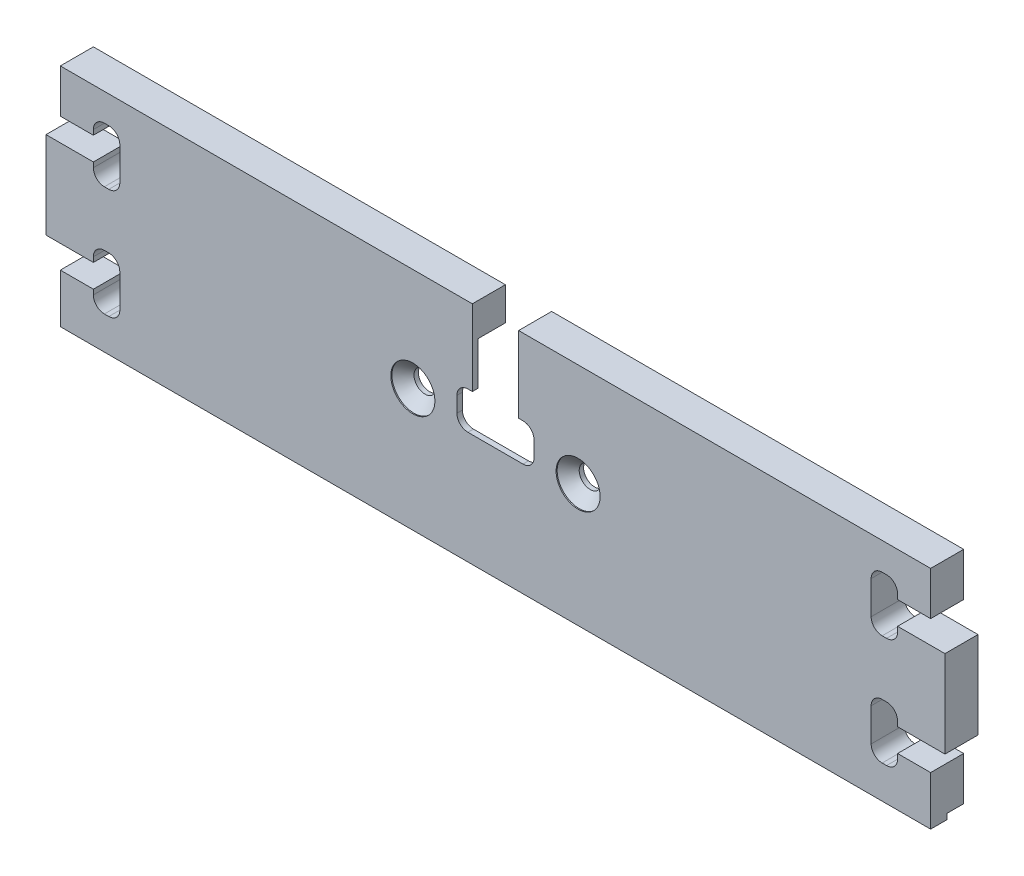
SolidWorks part; units mm, degrees
ref_plane "Front Plane" through (0, 0, 0) normal (0, 0, 1) x (1, 0, 0)
ref_plane "Top Plane" through (0, 0, 0) normal (0, 1, 0) x (1, 0, 0)
ref_plane "Right Plane" through (0, 0, 0) normal (1, 0, 0) x (0, 0, -1)
sketch "Sketch1" plane through (0, 0, 0) normal (0, 0, 1) x (1, 0, 0)
  line L0 (-39.5, 0) -> (39.5, 0) construction
  line L1 (-39.5, 10) -> (39.5, 10)
  line L2 (-39.5, 10) -> (-39.5, -10)
  line L3 (-39.5, -10) -> (39.5, -10)
  line L4 (39.5, 10) -> (39.5, -10)
  line L5 (-39.5, 10) -> (39.5, -10) construction
  line L6 (-39.5, -10) -> (39.5, 10) construction
  line L7 (0, 10) -> (0, -10) construction
  line L9 (-40.8, -3.95) -> (-39.5, -3.95)
  line L10 (-40.8, -3.95) -> (-40.8, 3.95)
  line L11 (-40.8, 3.95) -> (-39.5, 3.95)
  line L12 (-39.5, -3.95) -> (-39.5, 3.95)
  line L13 (-40.8, -3.95) -> (-39.5, 3.95) construction
  line L14 (-40.8, 3.95) -> (-39.5, -3.95) construction
  line L16 (40.8, 3.95) -> (39.5, 3.95)
  line L17 (40.8, -3.95) -> (40.8, 3.95)
  line L18 (40.8, -3.95) -> (39.5, -3.95)
  line L19 (-39.5, 5) -> (39.5, 5) construction
  line L20 (-35.3, 7.5) -> (-35.3, 2.5) construction
  line L21 (-36.5, 3.95) -> (-39.5, 3.95)
  line L22 (-36.5, 3.95) -> (-36.5, 6.05)
  line L23 (-36.5, 6.05) -> (-39.5, 6.05)
  line L24 (-39.5, 3.95) -> (-39.5, 6.05)
  line L25 (-36.5, 3.95) -> (-39.5, 6.05) construction
  line L26 (-36.5, 6.05) -> (-39.5, 3.95) construction
  line L27 (-34.1, 7.5) -> (-36.5, 7.5)
  line L28 (-34.1, 7.5) -> (-34.1, 2.5)
  line L29 (-34.1, 2.5) -> (-36.5, 2.5)
  line L30 (-36.5, 7.5) -> (-36.5, 2.5)
  line L31 (-34.1, 7.5) -> (-36.5, 2.5) construction
  line L32 (-34.1, 2.5) -> (-36.5, 7.5) construction
  line L33 (-34.1, -7.5) -> (-36.5, -7.5)
  line L34 (-34.1, -7.5) -> (-34.1, -2.5)
  line L35 (-34.1, -2.5) -> (-36.5, -2.5)
  line L36 (-36.5, -7.5) -> (-36.5, -2.5)
  line L37 (-36.5, -3.95) -> (-39.5, -3.95)
  line L38 (-36.5, -6.05) -> (-39.5, -6.05)
  line L39 (36.5, 3.95) -> (39.5, 3.95)
  line L40 (36.5, 6.05) -> (39.5, 6.05)
  line L41 (36.5, 7.5) -> (36.5, 2.5)
  line L42 (34.1, 7.5) -> (36.5, 7.5)
  line L43 (34.1, 7.5) -> (34.1, 2.5)
  line L44 (34.1, 2.5) -> (36.5, 2.5)
  line L45 (34.1, -2.5) -> (36.5, -2.5)
  line L46 (34.1, -7.5) -> (34.1, -2.5)
  line L47 (34.1, -7.5) -> (36.5, -7.5)
  line L48 (36.5, -7.5) -> (36.5, -2.5)
  line L49 (36.5, -6.05) -> (39.5, -6.05)
  line L50 (36.5, -3.95) -> (39.5, -3.95)
  point P0 (0, 0)
  point P10 (-40.15, 0)
  point P15 (-38, 5)
  point P35 (-35.3, 5)
  dimension "D1" = 79
  dimension "D2" = 20
  dimension "D4" = 1.3
  dimension "D7" = 5
  dimension "D8" = 2.1
  dimension "D9" = 3
  dimension "D10" = 2.4
  dimension "D11" = 5
extrude "Base shape" add sketch "Sketch1" along normal blind 3 contours L4 L1 L2 L3 | L9 L2 L11 L10 | L16 L4 L18 L17 region at (0, 0, 0) region at (-40.15, 0, 0) region at (40.15, 0, 0)
sketch "Sketch4" plane through (0, -10, 0) normal (0, -1, 0) x (1, 0, 0)
  line L0 (39.5, 3) -> (39.5, 0) construction
  line L1 (-39.5, 3) -> (39.5, 3)
  line L2 (-39.5, 3) -> (-39.5, 1.5)
  line L3 (-39.5, 1.5) -> (39.5, 1.5)
  line L4 (39.5, 3) -> (39.5, 1.5)
extrude "Floor lip" add sketch "Sketch4" along normal blind 0.5
sketch "Sketch6" plane through (0, 0, 0) normal (0, 0, -1) x (-1, 0, 0)
  line L0 (0, 0) -> (0, -10) construction
  line L1 (39.5, -10) -> (-39.5, -10) construction
  line L2 (-4, -10) -> (4, -10) construction
  line L3 (39.5, -10) -> (-39.5, -10) construction
  line L4 (-4, -9) -> (4, -9)
  line L5 (-4, -11) -> (4, -11)
  arc A0 (-4, -9) -> (-4, -11) centre (-4, -10) ccw
  arc A1 (4, -11) -> (4, -9) centre (4, -10) ccw
  point P9 (0, -10)
  dimension "D1" = 2
  dimension "D2" = 8
extrude "Nail cutout" cut sketch "Sketch6" against normal up to surface (1.5 mm away) up to face at (0, -10.25, 1.5)
sketch "Sketch3" plane through (-40.8, 0, 0) normal (-1, 0, 0) x (0, 0, 1)
  line L0 (0, 6.05) -> (3, 3.95) construction
  line L1 (0, 6.05) -> (3, 6.05)
  line L2 (0, 6.05) -> (0, 3.95)
  line L3 (0, 3.95) -> (3, 3.95)
  line L4 (3, 6.05) -> (3, 3.95)
  line L5 (0, -3.95) -> (3, -6.05) construction
  line L6 (0, -3.95) -> (3, -3.95)
  line L7 (0, -3.95) -> (0, -6.05)
  line L8 (0, -6.05) -> (3, -6.05)
  line L9 (3, -3.95) -> (3, -6.05)
  point P6 (1.5, 5)
  point P13 (1.5, -5)
ref_axis "Tap axis top" through (-53.7846, 5, 1.5) along (1, 0, 0)
ref_axis "Tap axis bottom" through (-54.2844, -5, 1.5) along (1, 0, 0)
fillet "Mill fillets" radius 1 16 edges at (36.5, -7.5, 1.5) (36.5, 2.5, 1.5) (34.1, 2.5, 1.5) (34.1, -7.5, 1.5) (36.5, -2.5, 1.5) (36.5, 7.5, 1.5) (34.1, -2.5, 1.5) (34.1, 7.5, 1.5) (-36.5, -2.5, 1.5) (-34.1, -2.5, 1.5) (-34.1, -7.5, 1.5) (-36.5, -7.5, 1.5) (-36.5, 2.5, 1.5) (-34.1, 2.5, 1.5) (-34.1, 7.5, 1.5) (-36.5, 7.5, 1.5)
sketch "Sketch8" [suppressed] plane through (0, 0, 3) normal (0, 0, 1) x (1, 0, 0)
  line L0 (-40.8, 0) -> (40.8, 0) construction
  line L1 (-40.8, -3.95) -> (-40.8, 3.95) construction
  line L2 (40.8, -3.95) -> (40.8, 3.95) construction
  line L4 (-24.5, 5.15) -> (24.5, 5.15)
  line L5 (-25.5, 4.15) -> (-25.5, -4.15)
  line L6 (-24.5, -5.15) -> (24.5, -5.15)
  line L7 (25.5, 4.15) -> (25.5, -4.15)
  line L8 (-25.5, 5.15) -> (25.5, -5.15) construction
  line L9 (-25.5, -5.15) -> (25.5, 5.15) construction
  arc A0 (24.5, -5.15) -> (25.5, -4.15) centre (24.5, -4.15) ccw
  arc A1 (24.5, 5.15) -> (25.5, 4.15) centre (24.5, 4.15) cw
  arc A2 (-25.5, -4.15) -> (-24.5, -5.15) centre (-24.5, -4.15) ccw
  arc A3 (-24.5, 5.15) -> (-25.5, 4.15) centre (-24.5, 4.15) ccw
  point P6 (0, 0)
  dimension "D3" = 1
  dimension "D1" = 51
  dimension "D2" = 10.3
extrude "Led strip pocket" [suppressed] cut sketch "Sketch8" against normal offset from surface (2.5 mm away) 0.5 up to face at (0, -0.6712, 0)
sketch "Sketch9" [suppressed] plane through (0, 0, 0.5) normal (0, 0, 1) x (1, 0, 0)
  line L0 (-19.5, 5.15) -> (-19.5, -5.15)
  line L1 (0, 5.15) -> (0, -5.15) construction
  line L2 (19.5, 5.15) -> (19.5, -5.15)
  line L3 (-25.5, -2.978) -> (25.5, -2.978) construction
  line L4 (25.5, -4.15) -> (25.5, 4.15)
  line L5 (24.5, 5.15) -> (-24.5, 5.15)
  line L6 (-25.5, 4.15) -> (-25.5, -4.15)
  line L7 (-24.5, -5.15) -> (24.5, -5.15)
  line L8 (25.5, -4.15) -> (25.5, 4.15)
  line L9 (24.5, 5.15) -> (-24.5, 5.15)
  line L10 (-25.5, 4.15) -> (-25.5, -4.15)
  line L11 (-24.5, -5.15) -> (24.5, -5.15)
  circle A0 centre (-12.7, -2.978) radius 1
  circle A1 centre (12.7, -2.978) radius 1
  arc A4 (24.5, -5.15) -> (25.5, -4.15) centre (24.5, -4.15) ccw
  arc A5 (25.5, 4.15) -> (24.5, 5.15) centre (24.5, 4.15) ccw
  arc A6 (-24.5, 5.15) -> (-25.5, 4.15) centre (-24.5, 4.15) ccw
  arc A7 (-25.5, -4.15) -> (-24.5, -5.15) centre (-24.5, -4.15) ccw
  arc A8 (24.5, -5.15) -> (25.5, -4.15) centre (24.5, -4.15) ccw
  arc A9 (25.5, 4.15) -> (24.5, 5.15) centre (24.5, 4.15) ccw
  arc A10 (-24.5, 5.15) -> (-25.5, 4.15) centre (-24.5, 4.15) ccw
  arc A11 (-25.5, -4.15) -> (-24.5, -5.15) centre (-24.5, -4.15) ccw
  arc M13 (24.5, -5.15) -> (25.5, -4.15) centre (24.5, -4.15) ccw
  line M14 (25.5, -4.15) -> (25.5, 4.15)
  arc M15 (25.5, 4.15) -> (24.5, 5.15) centre (24.5, 4.15) ccw
  line M16 (24.5, 5.15) -> (-24.5, 5.15)
  arc M17 (-24.5, 5.15) -> (-25.5, 4.15) centre (-24.5, 4.15) ccw
  line M18 (-25.5, 4.15) -> (-25.5, -4.15)
  arc M19 (-25.5, -4.15) -> (-24.5, -5.15) centre (-24.5, -4.15) ccw
  line M20 (-24.5, -5.15) -> (24.5, -5.15)
  dimension "D4" = 2
  dimension "D2" = 6
  dimension "D3" = 8.128
  dimension "D5" = 25.4
  dimension "D1" = 0
extrude "Led strip cuts" [suppressed] cut sketch "Sketch9" against normal up to next contours L0 M16 M17 M18 M19 M20 | L2 M16 M20 M13 M14 M15 | A0 | A1
fillet "Led strip cut fillets" [suppressed] radius 1
sketch "Sketch13" plane through (0, 0, 0) normal (0, 0, -1) x (-1, 0, 0)
  line L0 (0, 15.8648) -> (0, -21.9195) construction
  line L2 (-4.1, -5.7) -> (4.1, -5.7)
  line L3 (-5.1, -4.7) -> (-5.1, 6)
  line L4 (-4.1, 7) -> (4.1, 7)
  line L5 (5.1, -4.7) -> (5.1, 6)
  line L6 (-5.1, -5.7) -> (5.1, 7) construction
  line L7 (-5.1, 7) -> (5.1, -5.7) construction
  line L10 (39.5, 10) -> (-39.5, 10) construction
  arc A0 (-4.1, -5.7) -> (-5.1, -4.7) centre (-4.1, -4.7) cw
  arc A1 (4.1, -5.7) -> (5.1, -4.7) centre (4.1, -4.7) ccw
  arc A4 (5.1, 6) -> (4.1, 7) centre (4.1, 6) ccw
  arc A5 (-5.1, 6) -> (-4.1, 7) centre (-4.1, 6) cw
  point P1 (0, 0.65)
  point P8 (0, 0)
  point P9 (5.5684, 9.0125)
  point P16 (0, 0)
  point P17 (0, 0)
  dimension "D4" = 1
  dimension "D5" = 1
  dimension "D1" = 10.2
  dimension "D2" = 12.7
  dimension "D3" = 3
extrude "Bumper mount inner cut" cut sketch "Sketch13" against normal offset from surface (2.5 mm away) 0.5 up to face at (0, -0.0192, 3)
sketch "Sketch14" plane through (0, 0, 0) normal (0, 0, -1) x (-1, 0, 0)
  line L1 (0, 12.9528) -> (0, -14.0841) construction
  line L2 (4.1, 7) -> (-4.1, 7) construction
  line L3 (-4.1, -5.7) -> (4.1, -5.7) construction
  line L4 (-11.6, 7) -> (11.6, 7)
  line L5 (-12.6, 6) -> (-12.6, -4.7)
  line L6 (-11.6, -5.7) -> (11.6, -5.7)
  line L7 (12.6, 6) -> (12.6, -4.7)
  line L8 (-12.6, 7) -> (12.6, -5.7) construction
  line L9 (-12.6, -5.7) -> (12.6, 7) construction
  arc A1 (11.6, -5.7) -> (12.6, -4.7) centre (11.6, -4.7) ccw
  arc A2 (-12.6, -4.7) -> (-11.6, -5.7) centre (-11.6, -4.7) ccw
  arc A3 (11.6, 7) -> (12.6, 6) centre (11.6, 6) cw
  arc A4 (-12.6, 6) -> (-11.6, 7) centre (-11.6, 6) cw
  point P6 (0, 0.65)
  dimension "D2" = 1
  dimension "D3" = 1
  dimension "D1" = 25.2
extrude "Bumper mount outer cut" cut sketch "Sketch14" against normal blind 1.5
sketch "Sketch15" plane through (0, 0, 1.5) normal (0, 0, -1) x (-1, 0, 0)
  line L0 (-12.6, 0.65) -> (12.6, 0.65) construction
  line L3 (0, 16.4744) -> (0, -20.0474) construction
  line L4 (11.6, 7) -> (11.6, -5.7) construction
  line L6 (-11.6, -5.7) -> (11.6, -5.7) construction
  line L7 (-12.6, 6) -> (-12.6, -4.7) construction
  line L8 (12.6, -4.7) -> (12.6, 6) construction
  line L9 (11.6, 7) -> (4.1, 7) construction
  circle A0 centre (-7.5, 0.65) radius 1
  circle A1 centre (7.5, 0.65) radius 1
  point P2 (11.6, 0.65)
  point P5 (10, 7)
  point P13 (0, 0)
  point P19 (0, 0)
  point P22 (0, 0)
  point P24 (0, 0)
  point P25 (8.6174, -5.7)
  point P26 (0, 0)
  point P29 (0, 0)
  point P30 (13.4221, 7)
  dimension "D1" = 15
  dimension "D2" = 2
extrude "Bumper mount screw holes" cut sketch "Sketch15" against normal up to next
sketch "Sketch16" plane through (0, 0, 2.5) normal (0, 0, -1) x (-1, 0, 0)
  line L0 (-5.1, 1.4) -> (5.1, 1.4) construction
  line L3 (0, 7) -> (0, -4.2) construction
  line L4 (-2.5, 3.1) -> (2.5, 3.1)
  line L5 (-3.5, 2.1) -> (-3.5, 0.7)
  line L6 (-2.5, -0.3) -> (2.5, -0.3)
  line L7 (3.5, 2.1) -> (3.5, 0.7)
  line L8 (-3.5, 3.1) -> (3.5, -0.3) construction
  line L9 (-3.5, -0.3) -> (3.5, 3.1) construction
  line L11 (-5.1, 6) -> (-5.1, -4.7) construction
  line L13 (4.1, 7) -> (-4.1, 7) construction
  arc A0 (2.5, -0.3) -> (3.5, 0.7) centre (2.5, 0.7) ccw
  arc A1 (-3.5, 0.7) -> (-2.5, -0.3) centre (-2.5, 0.7) ccw
  arc A2 (-2.5, 3.1) -> (-3.5, 2.1) centre (-2.5, 2.1) ccw
  arc A3 (2.5, 3.1) -> (3.5, 2.1) centre (2.5, 2.1) cw
  point P2 (0, 0)
  point P5 (0, 0)
  point P6 (0, 1.4)
  point P23 (0, 0)
  point P24 (0, 7.9459)
  point P29 (0, 0)
  dimension "D3" = 1
  dimension "D1" = 7
  dimension "D2" = 3.4
  dimension "D4" = 11.2
extrude "Bumper body cut" cut sketch "Sketch16" against normal up to next
hole_wizard "Bumper screw countersunks" positions "Sketch17" profile "Sketch18" countersink size "M2" standard "ANSI Metric" end condition through all
sketch "Sketch17" plane through (0, 0, 3) normal (0, 0, 1) x (1, 0, 0)
  point P0 (7.5, 0.65)
  point P3 (-7.5, 0.65)
sketch "Sketch18" plane through (7.5, 0.65, 3) normal (1, 0, 0) x (0, -1, 0)
  line L0 (0, 0) -> (0, 3)
  line L1 (0, 3) -> (1, 3)
  line L2 (1, 3) -> (1, 1.1)
  line L3 (1, 1.1) -> (2, 0.1)
  line L4 (2, 0.1) -> (2, 0)
  line L6 (2, 0) -> (0, 0)
  line L7 (-1, 1.1) -> (-2, 0.1) construction
  line L11 (0, -6.35) -> (0, 107.95) construction
  dimension "Thru Hole Dia." = 2
  dimension "Thru Hole Depth" = 3
  dimension "C'Sink Dia." = 4
  dimension "C'Sink Angle" = 90
  dimension "Head Clearance" = 0.1
sketch "Sketch19" plane through (0, 0, 0) normal (0, 0, -1) x (-1, 0, 0)
  line L0 (0, 15.6498) -> (0, -12.9575) construction
  line L1 (39.5, 10) -> (-39.5, 10) construction
  line L2 (-2.1, 3.1) -> (2.1, 3.1)
  line L3 (-2.1, 3.1) -> (-2.1, 10)
  line L4 (-2.1, 10) -> (2.1, 10)
  line L5 (2.1, 3.1) -> (2.1, 10)
  line L6 (-2.1, 3.1) -> (2.1, 10) construction
  line L7 (-2.1, 10) -> (2.1, 3.1) construction
  line L8 (2.5, 3.1) -> (-2.5, 3.1) construction
  point P1 (0, 6.55)
  dimension "D1" = 4.2
extrude "Bumper insertion cut" cut sketch "Sketch19" against normal up to next
